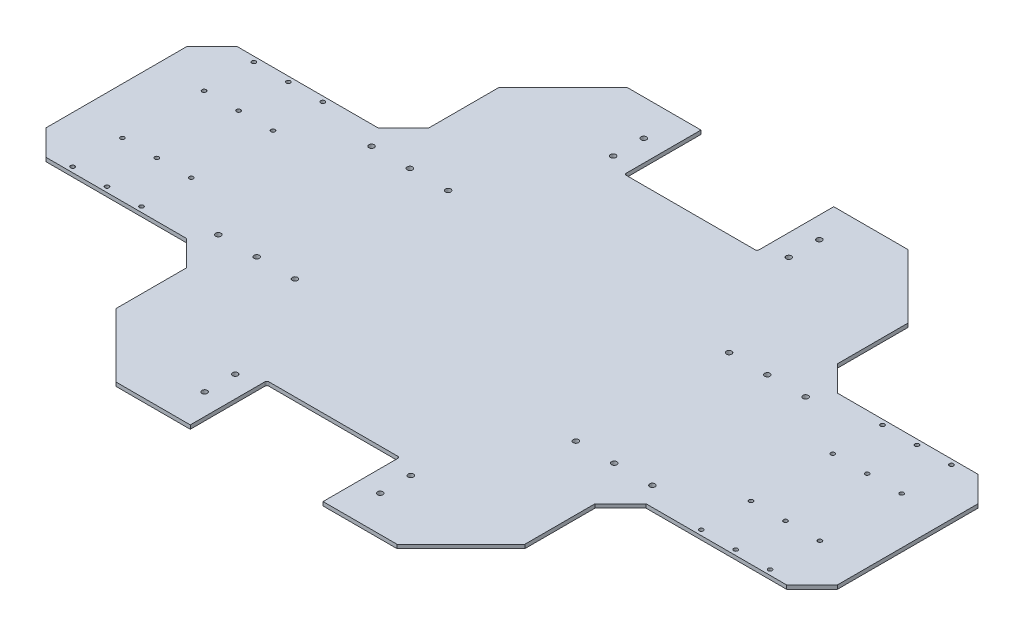
SolidWorks part; units mm, degrees
ref_plane "前视基准面" through (0, 0, 0) normal (0, 0, 1) x (1, 0, 0)
ref_plane "上视基准面" through (0, 0, 0) normal (0, 1, 0) x (1, 0, 0)
ref_plane "右视基准面" through (0, 0, 0) normal (1, 0, 0) x (0, 0, -1)
sketch "草图1" plane through (0, 0, 0) normal (0, 1, 0) x (1, 0, 0)
  line L0 (0, 0) -> (160, -38.7097) construction
  line L1 (-260, 200) -> (260, 200) construction
  line L2 (-260, 200) -> (-260, -200) construction
  line L3 (-260, -200) -> (260, -200) construction
  line L4 (260, 200) -> (260, -200) construction
  line L5 (-260, 200) -> (-160, 123.0769) construction
  line L6 (-260, -200) -> (-160, -123.0769) construction
  line L7 (-310, -75) -> (-160, -75)
  line L8 (-310, -75) -> (-310, 75)
  line L9 (-310, 75) -> (-160, 75)
  line L10 (310, -75) -> (310, 75)
  line L11 (-310, -75) -> (160, 38.7097) construction
  line L12 (-310, 75) -> (-160, 38.7097) construction
  line L13 (-160, -200) -> (160, -200)
  line L14 (-160, -200) -> (-160, -75)
  line L15 (-160, 200) -> (160, 200)
  line L16 (160, -200) -> (160, -75)
  line L17 (-60, -75) -> (0, 0) construction
  line L18 (0, 0) -> (60, -75) construction
  line L19 (-160, 75) -> (-160, 200)
  line L22 (160, 75) -> (310, 75)
  line L24 (97.5, 75) -> (260, 200) construction
  line L25 (160, 75) -> (160, 200)
  line L26 (260, 62.9032) -> (310, 75) construction
  line L27 (260, -62.9032) -> (310, -75) construction
  line L28 (160, -75) -> (310, -75)
  line L29 (160, -123.0769) -> (260, -200) construction
  point P0 (0, 0)
  point P6 (0, 0)
  point P11 (0, 0)
  dimension "D1" = 520
  dimension "D2" = 400
  dimension "D3" = 50
  dimension "D4" = 125
  dimension "D5" = 100
extrude "凸台-拉伸1" add sketch "草图1" along normal blind 3
chamfer "倒角1" distance 20 angle 45 8 edges at (-160, 1.5, -75) (-310, 1.5, -75) (-310, 1.5, 75) (-160, 1.5, 75) (160, 1.5, 75) (160, 1.5, -75) (310, 1.5, 75) (310, 1.5, -75)
chamfer "倒角2" distance 50 angle 45 4 edges at (160, 1.5, 200) (-160, 1.5, 200) (160, 1.5, -200) (-160, 1.5, -200)
sketch "草图2" plane through (0, 0, 0) normal (0, -1, 0) x (-1, 0, 0)
  line L1 (52, -140) -> (-52, -140)
  line L2 (52, -140) -> (52, -233.0888)
  line L3 (52, -233.0888) -> (-52, -233.0888)
  line L4 (-52, -140) -> (-52, -233.0888)
  line L6 (0, 0) -> (119.8246, 0) construction
  line L7 (-52, 140) -> (-52, 233.0888)
  line L8 (52, 233.0888) -> (-52, 233.0888)
  line L9 (52, 140) -> (52, 233.0888)
  line L10 (52, 140) -> (-52, 140)
  line L11 (160, -95) -> (160, -150) construction
  line L12 (-160, -150) -> (-160, -95) construction
  dimension "D1" = 108
  dimension "D2" = 108
extrude "切除-拉伸1" cut sketch "草图2" against normal blind 40
fillet "圆角1" radius 1.5 4 edges at (-52, 1.5, -140) (52, 1.5, -140) (52, 1.5, 140) (-52, 1.5, 140)
sketch "草图3" plane through (0, 0, 0) normal (0, -1, 0) x (1, 0, 0)
  circle A0 centre (-68.75, 172) radius 2.1
  circle A1 centre (-68.75, 148) radius 2.1
  circle A2 centre (68.75, 172) radius 2.1
  circle A3 centre (68.75, 148) radius 2.1
  circle A4 centre (-68.75, -148) radius 2.1
  circle A5 centre (-68.75, -172) radius 2.1
  circle A6 centre (68.75, -148) radius 2.1
  circle A7 centre (68.75, -172) radius 2.1
extrude "切除-拉伸2" cut sketch "草图3" against normal blind 80
sketch "草图4" plane through (0, 0, 0) normal (0, -1, 0) x (1, 0, 0)
  line L0 (0, 0) -> (124.2092, 0) construction
  line L1 (0, 0) -> (0, 63.2758) construction
  circle A0 centre (273.2002, 71) radius 1.6
  circle A1 centre (273.2002, 31.9984) radius 1.6
  circle A2 centre (246.2002, 71) radius 1.6
  circle A3 centre (219.2002, 71) radius 1.6
  circle A4 centre (246.2002, 31.9984) radius 1.6
  circle A5 centre (219.2002, 31.9984) radius 1.6
  circle A6 centre (110, 60) radius 2.1
  circle A7 centre (140, 60) radius 2.1
  circle A8 centre (170, 60) radius 2.1
  circle A9 centre (170, -60) radius 2.1
  circle A10 centre (140, -60) radius 2.1
  circle A11 centre (110, -60) radius 2.1
  circle A12 centre (219.2002, -31.9984) radius 1.6
  circle A13 centre (246.2002, -31.9984) radius 1.6
  circle A14 centre (219.2002, -71) radius 1.6
  circle A15 centre (246.2002, -71) radius 1.6
  circle A16 centre (273.2002, -31.9984) radius 1.6
  circle A17 centre (273.2002, -71) radius 1.6
  circle A18 centre (-273.2002, -71) radius 1.6
  circle A19 centre (-273.2002, -31.9984) radius 1.6
  circle A20 centre (-246.2002, -71) radius 1.6
  circle A21 centre (-219.2002, -71) radius 1.6
  circle A22 centre (-246.2002, -31.9984) radius 1.6
  circle A23 centre (-219.2002, -31.9984) radius 1.6
  circle A24 centre (-110, -60) radius 2.1
  circle A25 centre (-140, -60) radius 2.1
  circle A26 centre (-170, -60) radius 2.1
  circle A27 centre (-170, 60) radius 2.1
  circle A28 centre (-140, 60) radius 2.1
  circle A29 centre (-110, 60) radius 2.1
  circle A30 centre (-219.2002, 31.9984) radius 1.6
  circle A31 centre (-246.2002, 31.9984) radius 1.6
  circle A32 centre (-219.2002, 71) radius 1.6
  circle A33 centre (-246.2002, 71) radius 1.6
  circle A34 centre (-273.2002, 31.9984) radius 1.6
  circle A35 centre (-273.2002, 71) radius 1.6
extrude "切除-拉伸3" cut sketch "草图4" against normal blind 29
